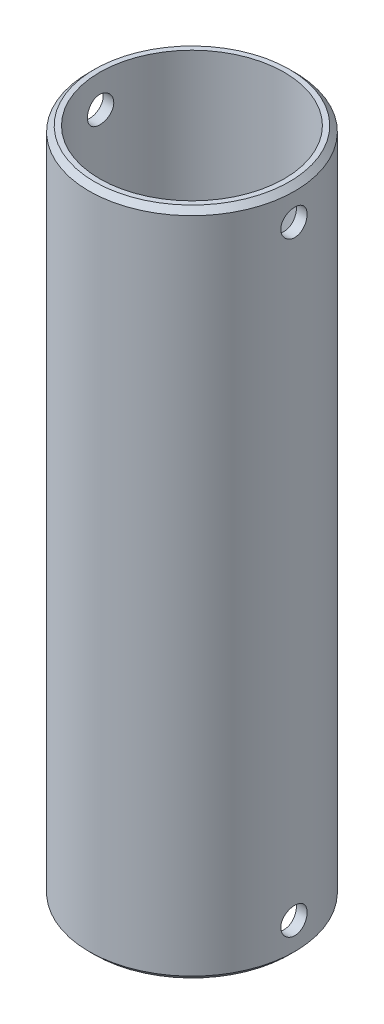
SolidWorks part; units mm, degrees
material "AISI 304 Stainless Steel"
ref_plane "Front Plane" through (0, 0, 0) normal (0, 0, 1) x (1, 0, 0)
ref_plane "Top Plane" through (0, 0, 0) normal (0, 1, 0) x (1, 0, 0)
ref_plane "Right Plane" through (0, 0, 0) normal (1, 0, 0) x (0, 0, -1)
ref_axis "Axis1" through (0, 0, -88.99) along (0, 0, 1)
ref_axis "Axis2" through (0, -55, 0) along (0, 1, 0)
ref_axis "Axis3" through (-88.99, 0, 0) along (1, 0, 0)
sketch "Sketch1" plane through (0, 0, 0) normal (0, 1, 0) x (1, 0, 0)
  circle A0 centre (0, 0) radius 9.525
  circle A1 centre (0, 0) radius 8.5471
  dimension "D1" = 19.05
  dimension "D2" = 0.9779
extrude "Boss-Extrude1" add sketch "Sketch1" along normal mid plane 62 contours A0 A1 region at (-9.2556, 0, 0)
ref_plane "Plane1" through (-9.525, 0, 0) normal (-1, 0, 0) x (0, 0, 1)
hole_wizard "#41 (0.096) Diameter Hole1" positions "Sketch3" profile "Sketch2" hole size "#41" standard "ANSI Inch" end condition through all
sketch "Sketch3" plane through (-9.525, 0, 0) normal (-1, 0, 0) x (0, 0, 1)
  line L0 (0, 31) -> (0, 0) construction
  line L1 (8.5471, 31) -> (-8.5471, 31) construction
  line L2 (0, 0) -> (9.525, 0) construction
  line L3 (9.525, -31) -> (9.525, 31) construction
  line L5 (9.525, 31) -> (-9.525, 31) construction
  point P0 (0, 28)
  point P2 (0, -28)
  dimension "D1" = 3
sketch "Sketch2" plane through (-9.525, 28, 0) normal (0, 1, 0) x (0, 0, 1)
  line L0 (0, 0) -> (0, 19.05)
  line L1 (0, 19.05) -> (1.2192, 19.05)
  line L2 (1.2192, 19.05) -> (1.2192, 0)
  line L5 (1.2192, 0) -> (0, 0)
  line L11 (0, -6.35) -> (0, 107.95) construction
  dimension "Thru Hole Dia." = 2.4384
  dimension "Thru Hole Depth" = 19.05
chamfer "Chamfer1" distance 0.5 angle 45 2 edges at (0, 31, 9.525) (0, -31, 9.525)
